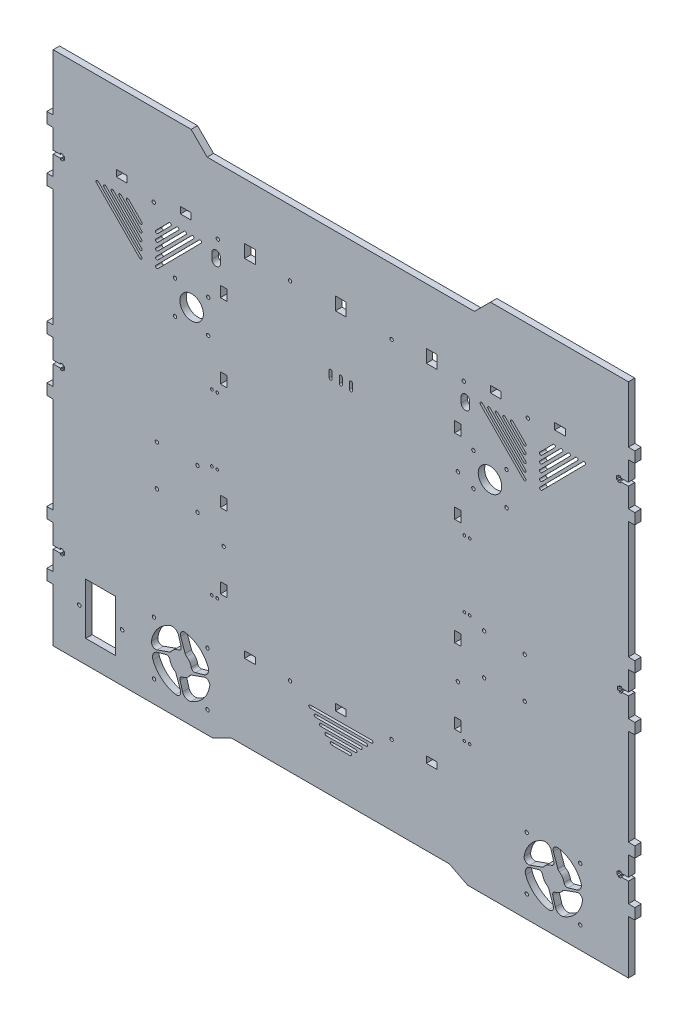
SolidWorks part; units mm, degrees
material "Клен"
ref_plane "Front" through (0, 0, 0) normal (0, 0, 1) x (1, 0, 0)
ref_plane "Top" through (0, 0, 0) normal (0, 1, 0) x (1, 0, 0)
ref_plane "Right" through (0, 0, 0) normal (1, 0, 0) x (0, 0, -1)
sketch "Эскиз1" plane through (0, 0, 0) normal (0, 0, 1) x (1, 0, 0)
  line L3 (1048.7554, 41.5559) -> (1198.2753, 41.5559)
  line L12 (1586.7554, 42.2299) -> (1586.7554, 41.5559)
  line L13 (1397.7554, 445.0072) -> (1407.7554, 445.0072)
  line L14 (1407.7554, 445.0072) -> (1407.7554, 457.1072)
  line L15 (1407.7554, 457.1072) -> (1397.7554, 457.1072)
  line L16 (1397.7554, 457.1072) -> (1397.7554, 445.0072)
  line L17 (1048.7554, 42.2256) -> (1048.7554, 41.5559)
  line L18 (1197.1554, 434.4743) -> (1197.1554, 429.1914)
  line L19 (1503.9666, 426.2291) -> (1516.2724, 438.6716)
  line L20 (1546.3337, 437.0699) -> (1505.9003, 396.1873)
  line L21 (1227.7554, 445.0072) -> (1237.7554, 445.0072)
  line L22 (1237.7554, 445.0072) -> (1237.7554, 457.1072)
  line L23 (1237.7554, 457.1072) -> (1227.7554, 457.1072)
  line L24 (1227.7554, 457.1072) -> (1227.7554, 445.0072)
  line L25 (1312.7554, 445.0072) -> (1322.7554, 445.0072)
  line L26 (1322.7554, 445.0072) -> (1322.7554, 457.1072)
  line L27 (1322.7554, 457.1072) -> (1312.7554, 457.1072)
  line L28 (1312.7554, 457.1072) -> (1312.7554, 445.0072)
  line L38 (1525.1209, 436.9527) -> (1505.7831, 417.4001)
  line L41 (1504.0838, 405.0162) -> (1537.4853, 438.7888)
  line L43 (1504.1228, 397.9452) -> (1544.5562, 438.8279)
  line L44 (1504.0056, 419.1581) -> (1523.3433, 438.7107)
  line L48 (1167.7554, 451.0072) -> (1177.7554, 451.0072)
  line L49 (1177.7554, 451.0072) -> (1177.7554, 457.1072)
  line L50 (1177.7554, 457.1072) -> (1167.7554, 457.1072)
  line L51 (1167.7554, 457.1072) -> (1167.7554, 451.0072)
  line L52 (1518.0499, 436.9136) -> (1505.7441, 424.4711)
  line L53 (1532.1918, 436.9918) -> (1505.8222, 410.3292)
  line L54 (1539.2628, 437.0308) -> (1505.8613, 403.2582)
  line L55 (1504.0447, 412.0872) -> (1530.4143, 438.7498)
  line L56 (1457.7554, 451.0072) -> (1467.7554, 451.0072)
  line L57 (1467.7554, 451.0072) -> (1467.7554, 457.1072)
  line L58 (1467.7554, 457.1072) -> (1457.7554, 457.1072)
  line L59 (1457.7554, 457.1072) -> (1457.7554, 451.0072)
  line L78 (1131.3881, 397.9452) -> (1090.9547, 438.8279)
  line L80 (1089.1772, 437.0699) -> (1129.6105, 396.1873)
  line L82 (1096.2481, 437.0308) -> (1129.6496, 403.2582)
  line L83 (1131.4271, 405.0162) -> (1098.0256, 438.7888)
  line L84 (1131.4662, 412.0872) -> (1105.0966, 438.7498)
  line L85 (1103.3191, 436.9918) -> (1129.6887, 410.3292)
  line L86 (1131.5052, 419.1581) -> (1112.1675, 438.7107)
  line L87 (1110.39, 436.9527) -> (1129.7277, 417.4001)
  line L88 (1131.5443, 426.2291) -> (1119.2385, 438.6716)
  line L89 (1117.461, 436.9136) -> (1129.7668, 424.4711)
  line L90 (1144.921, 397.9452) -> (1185.3543, 438.8279)
  line L91 (1187.1318, 437.0699) -> (1146.6985, 396.1873)
  line L92 (1397.7554, 121.0049) -> (1407.7554, 121.0049)
  line L93 (1407.7554, 121.0049) -> (1407.7554, 127.1049)
  line L94 (1407.7554, 127.1049) -> (1397.7554, 127.1049)
  line L95 (1397.7554, 127.1049) -> (1397.7554, 121.0049)
  line L96 (1312.7554, 121.0049) -> (1322.7554, 121.0049)
  line L97 (1322.7554, 121.0049) -> (1322.7554, 127.1049)
  line L98 (1322.7554, 127.1049) -> (1312.7554, 127.1049)
  line L99 (1312.7554, 127.1049) -> (1312.7554, 121.0049)
  line L100 (1227.7554, 121.0049) -> (1237.7554, 121.0049)
  line L101 (1237.7554, 121.0049) -> (1237.7554, 127.1049)
  line L102 (1237.7554, 127.1049) -> (1227.7554, 127.1049)
  line L143 (1227.7554, 127.1049) -> (1227.7554, 121.0049)
  line L148 (1079.1628, 110.8776) -> (1079.1628, 62.8776)
  line L154 (1455.45, 437.0308) -> (1488.8515, 403.2582)
  line L159 (1107.1628, 110.8776) -> (1079.1628, 110.8776)
  line L160 (1079.1628, 62.8776) -> (1107.1628, 62.8776)
  line L161 (1107.1628, 62.8776) -> (1107.1628, 110.8776)
  line L162 (1144.8819, 405.0162) -> (1178.2834, 438.7888)
  line L163 (1180.0609, 437.0308) -> (1146.6594, 403.2582)
  line L164 (1172.9899, 436.9918) -> (1146.6203, 410.3292)
  line L165 (1144.8428, 412.0872) -> (1171.2124, 438.7498)
  line L166 (1144.8038, 419.1581) -> (1164.1415, 438.7107)
  line L167 (1165.919, 436.9527) -> (1146.5813, 417.4001)
  line L168 (1158.848, 436.9136) -> (1146.5422, 424.4711)
  line L169 (1144.7647, 426.2291) -> (1157.0705, 438.6716)
  line L170 (1205.1554, 429.1914) -> (1205.1554, 434.4743)
  line L171 (1430.3554, 429.1914) -> (1430.3554, 434.4743)
  line L172 (1326.6292, 91.6177) -> (1309.1294, 91.521)
  line L173 (1309.1156, 94.021) -> (1326.6154, 94.1176)
  line L174 (1331.6015, 96.6452) -> (1304.1019, 96.4933)
  line L175 (1304.0881, 98.9933) -> (1331.5877, 99.1452)
  line L176 (1336.5738, 101.6728) -> (1299.0744, 101.4656)
  line L177 (1299.0605, 103.9656) -> (1336.56, 104.1727)
  line L178 (1289.0054, 113.9102) -> (1346.5046, 114.2278)
  line L179 (1346.5184, 111.7279) -> (1289.0193, 111.4102)
  line L180 (1341.5461, 106.7003) -> (1294.0468, 106.4379)
  line L181 (1294.033, 108.9379) -> (1341.5323, 109.2003)
  line L182 (1490.629, 405.0162) -> (1457.2275, 438.7888)
  line L183 (1448.379, 437.0699) -> (1488.8124, 396.1873)
  line L184 (1469.5919, 436.9527) -> (1488.9296, 417.4001)
  line L185 (1476.6629, 436.9136) -> (1488.9687, 424.4711)
  line L186 (1490.5899, 397.9452) -> (1450.1565, 438.8279)
  line L187 (1490.7071, 419.1581) -> (1471.3694, 438.7107)
  line L188 (1462.521, 436.9918) -> (1488.8906, 410.3292)
  line L189 (1490.7462, 426.2291) -> (1478.4404, 438.6716)
  line L198 (1530.3174, 86.3769) -> (1538.4752, 88.7337)
  line L199 (1494.5571, 86.9094) -> (1506.2002, 91.0661)
  line L200 (1517.0418, 100.6255) -> (1514.685, 108.7833)
  line L201 (1502.7664, 87.3542) -> (1494.6086, 84.9974)
  line L202 (1538.538, 86.8062) -> (1526.8948, 82.6495)
  line L203 (1516.0532, 73.09) -> (1518.4101, 64.9322)
  line L204 (1516.4826, 64.8695) -> (1512.3258, 76.5127)
  line L205 (1516.6012, 108.8616) -> (1520.758, 97.2184)
  line L210 (1215.2753, 50.2559) -> (1198.2753, 41.5559)
  line L268 (1215.2753, 50.2559) -> (1419.2753, 50.2559)
  line L269 (1419.2753, 50.2559) -> (1436.2753, 41.5559)
  line L270 (1436.2753, 41.5559) -> (1586.7554, 41.5559)
  line L271 (1490.6681, 412.0872) -> (1464.2985, 438.7498)
  line L302 (1527.7554, 457.1072) -> (1517.7554, 457.1072)
  line L303 (1517.7554, 451.0072) -> (1527.7554, 451.0072)
  line L304 (1517.7554, 457.1072) -> (1517.7554, 451.0072)
  line L305 (1527.7554, 451.0072) -> (1527.7554, 457.1072)
  line L306 (1117.7554, 451.0072) -> (1117.7554, 457.1072)
  line L307 (1107.7554, 457.1072) -> (1107.7554, 451.0072)
  line L308 (1117.7554, 457.1072) -> (1107.7554, 457.1072)
  line L309 (1107.7554, 451.0072) -> (1117.7554, 451.0072)
  line L310 (1167.825, 64.8695) -> (1163.6683, 76.5127)
  line L331 (1438.3554, 434.4743) -> (1438.3554, 429.1914)
  line L332 (1592.7554, 85.0176) -> (1592.7554, 537.1765) construction
  line L333 (989.7428, 524.5559) -> (1177.7554, 524.5559) construction
  line L335 (1048.7554, 524.5559) -> (1177.7554, 524.5559)
  line L337 (1048.7554, 524.5559) -> (1048.7554, 471.6559)
  line L338 (1586.7554, 524.5559) -> (1586.7554, 471.6484)
  line L339 (1442.7554, 509.5559) -> (1457.7554, 524.5559)
  line L342 (1192.7554, 509.5559) -> (1442.7554, 509.5559)
  line L346 (1192.7554, 509.5559) -> (1177.7554, 524.5559)
  line L348 (1592.7554, 461.5645) -> (1586.7554, 461.472)
  line L349 (1457.7554, 524.5559) -> (1617.7234, 524.5559) construction
  line L350 (1457.7554, 524.5559) -> (1586.7554, 524.5559)
  line L358 (1059.2554, 440.0059) -> (1059.2554, 443.1059)
  line L359 (1057.7554, 438.8059) -> (1057.7554, 440.0059)
  line L361 (1057.7554, 270.0059) -> (1059.2554, 270.0059)
  line L362 (1055.5554, 270.0059) -> (1055.5554, 268.8059)
  line L363 (1430.3554, 401.9072) -> (1430.3554, 411.9072)
  line L364 (1430.3554, 411.9072) -> (1424.2554, 411.9072)
  line L365 (1424.2554, 411.9072) -> (1424.2554, 401.9072)
  line L366 (1424.2554, 401.9072) -> (1430.3554, 401.9072)
  line L367 (1430.3554, 331.9072) -> (1430.3554, 341.9072)
  line L368 (1430.3554, 341.9072) -> (1424.2554, 341.9072)
  line L369 (1424.2554, 341.9072) -> (1424.2554, 331.9072)
  line L370 (1424.2554, 331.9072) -> (1430.3554, 331.9072)
  line L371 (1430.3554, 231.9072) -> (1430.3554, 241.9072)
  line L372 (1430.3554, 241.9072) -> (1424.2554, 241.9072)
  line L373 (1424.2554, 241.9072) -> (1424.2554, 231.9072)
  line L374 (1424.2554, 231.9072) -> (1430.3554, 231.9072)
  line L375 (1424.2554, 171.9072) -> (1424.2554, 161.9072)
  line L376 (1424.2554, 161.9072) -> (1430.3554, 161.9072)
  line L377 (1430.3554, 161.9072) -> (1430.3554, 171.9072)
  line L378 (1430.3554, 171.9072) -> (1424.2554, 171.9072)
  line L379 (1205.1554, 161.9072) -> (1211.2554, 161.9072)
  line L380 (1211.2554, 161.9072) -> (1211.2554, 171.9072)
  line L381 (1205.1554, 171.9072) -> (1205.1554, 161.9072)
  line L382 (1211.2554, 171.9072) -> (1205.1554, 171.9072)
  line L383 (1211.2554, 231.9072) -> (1211.2554, 241.9072)
  line L384 (1211.2554, 241.9072) -> (1205.1554, 241.9072)
  line L385 (1205.1554, 241.9072) -> (1205.1554, 231.9072)
  line L386 (1205.1554, 231.9072) -> (1211.2554, 231.9072)
  line L387 (1205.1554, 331.9072) -> (1211.2554, 331.9072)
  line L388 (1211.2554, 331.9072) -> (1211.2554, 341.9072)
  line L389 (1205.1554, 341.9072) -> (1205.1554, 331.9072)
  line L390 (1211.2554, 341.9072) -> (1205.1554, 341.9072)
  line L391 (1205.1554, 401.9072) -> (1211.2554, 401.9072)
  line L392 (1211.2554, 401.9072) -> (1211.2554, 411.9072)
  line L393 (1211.2554, 411.9072) -> (1205.1554, 411.9072)
  line L394 (1205.1554, 411.9072) -> (1205.1554, 401.9072)
  line L395 (1145.8995, 86.9094) -> (1157.5427, 91.0661)
  line L396 (1189.8804, 86.8062) -> (1178.2373, 82.6495)
  line L397 (1167.3957, 73.09) -> (1169.7525, 64.9322)
  line L398 (1154.1089, 87.3542) -> (1145.951, 84.9974)
  line L399 (1181.6599, 86.3769) -> (1189.8177, 88.7337)
  line L400 (1167.9437, 108.8616) -> (1172.1004, 97.2184)
  line L414 (1057.7554, 118.8059) -> (1057.7554, 120.0059)
  line L415 (1168.3843, 100.6255) -> (1166.0274, 108.7833)
  line L416 (1317.7554, 12.4246) -> (1317.7554, 537.1765) construction
  line L417 (1586.7554, 537.1765) -> (1586.7554, 12.4246) construction
  line L418 (1048.7554, 537.1765) -> (1048.7554, -11.6164) construction
  line L419 (1042.7554, 91.5559) -> (1042.7554, 101.5559)
  line L422 (1048.7554, 123.1059) -> (1048.7554, 141.4559)
  line L426 (1059.2554, 123.1059) -> (1057.7554, 123.1059)
  line L427 (1057.7554, 274.3059) -> (1055.5554, 274.3059)
  line L428 (1325.8554, 394.0442) -> (1325.8554, 388.0442)
  line L429 (1328.6554, 388.0442) -> (1328.6554, 394.0442)
  line L430 (1042.7554, 101.5559) -> (1048.7554, 101.6559)
  line L431 (1057.7554, 120.0059) -> (1059.2554, 120.0059)
  line L432 (1316.3554, 394.0442) -> (1316.3554, 388.0442)
  line L433 (1319.1554, 388.0442) -> (1319.1554, 394.0442)
  line L434 (1042.7554, 141.5559) -> (1042.7554, 151.5559)
  line L435 (1042.7554, 301.5559) -> (1048.7554, 301.6559)
  line L436 (1306.8554, 394.0442) -> (1306.8554, 388.0442)
  line L437 (1309.6554, 388.0442) -> (1309.6554, 394.0442)
  line L438 (1055.5554, 120.0059) -> (1055.5554, 118.8059)
  line L439 (1048.7554, 411.4559) -> (1042.7554, 411.5559)
  line L440 (1055.5554, 444.3059) -> (1055.5554, 443.1059)
  line L441 (1057.7554, 124.3059) -> (1055.5554, 124.3059)
  line L442 (1055.5554, 443.1059) -> (1048.7554, 443.1059)
  line L443 (1048.7554, 120.0059) -> (1055.5554, 120.0059)
  line L444 (1042.7554, 241.5559) -> (1042.7554, 251.5559)
  line L445 (1055.5554, 268.8059) -> (1057.7554, 268.8059)
  line L446 (1055.5554, 274.3059) -> (1055.5554, 273.1059)
  line L447 (1048.7554, 461.4559) -> (1042.7554, 461.5559)
  line L448 (1048.7554, 101.6559) -> (1048.7554, 120.0059)
  line L449 (1057.7554, 440.0059) -> (1059.2554, 440.0059)
  line L450 (1048.7554, 251.6559) -> (1048.7554, 270.0059)
  line L451 (1042.7554, 291.5559) -> (1042.7554, 301.5559)
  line L452 (1042.7554, 471.5559) -> (1048.7554, 471.6559)
  line L453 (1059.2554, 443.1059) -> (1057.7554, 443.1059)
  line L454 (1048.7554, 42.2256) -> (1048.7554, 91.4559)
  line L455 (1048.7554, 273.1059) -> (1048.7554, 291.4559)
  line L456 (1055.5554, 440.0059) -> (1055.5554, 438.8059)
  line L457 (1055.5554, 438.8059) -> (1057.7554, 438.8059)
  line L458 (1042.7554, 421.5559) -> (1048.7554, 421.6559)
  line L459 (1048.7554, 443.1059) -> (1048.7554, 461.4559)
  line L460 (1048.7554, 141.4559) -> (1042.7554, 141.5559)
  line L461 (1048.7554, 301.6559) -> (1048.7554, 411.4559)
  line L462 (1048.7554, 91.4559) -> (1042.7554, 91.5559)
  line L463 (1048.7554, 270.0059) -> (1055.5554, 270.0059)
  line L464 (1048.7554, 291.4559) -> (1042.7554, 291.5559)
  line L465 (1059.2554, 120.0059) -> (1059.2554, 123.1059)
  line L466 (1057.7554, 273.1059) -> (1057.7554, 274.3059)
  line L467 (1042.7554, 251.5559) -> (1048.7554, 251.6559)
  line L468 (1059.2554, 273.1059) -> (1057.7554, 273.1059)
  line L469 (1048.7554, 421.6559) -> (1048.7554, 440.0059)
  line L470 (1042.7554, 461.5559) -> (1042.7554, 471.5559)
  line L471 (1057.7554, 268.8059) -> (1057.7554, 270.0059)
  line L472 (1057.7554, 443.1059) -> (1057.7554, 444.3059)
  line L473 (1042.7554, 151.5559) -> (1048.7554, 151.6559)
  line L474 (1059.2554, 270.0059) -> (1059.2554, 273.1059)
  line L475 (1055.5554, 273.1059) -> (1048.7554, 273.1059)
  line L476 (1048.7554, 151.6559) -> (1048.7554, 241.4559)
  line L477 (1057.7554, 444.3059) -> (1055.5554, 444.3059)
  line L478 (1055.5554, 124.3059) -> (1055.5554, 123.1059)
  line L479 (1048.7554, 241.4559) -> (1042.7554, 241.5559)
  line L480 (1055.5554, 123.1059) -> (1048.7554, 123.1059)
  line L481 (1057.7554, 123.1059) -> (1057.7554, 124.3059)
  line L482 (1055.5554, 118.8059) -> (1057.7554, 118.8059)
  line L483 (1042.7554, 411.5559) -> (1042.7554, 421.5559)
  line L484 (1048.7554, 440.0059) -> (1055.5554, 440.0059)
  line L488 (1586.7554, 301.6559) -> (1592.7554, 301.5559)
  line L489 (1592.7554, 251.5803) -> (1592.7554, 241.5722)
  line L490 (1579.2472, 444.3102) -> (1577.0472, 444.3102)
  line L491 (1592.7554, 471.5559) -> (1592.7554, 461.5645)
  line L492 (1579.9554, 120.0141) -> (1586.7554, 120.0141)
  line L493 (1592.7554, 101.5641) -> (1592.7554, 91.5559)
  line L494 (1579.9554, 123.1141) -> (1579.9554, 124.3141)
  line L496 (1577.7554, 120.0141) -> (1577.7554, 118.8141)
  line L497 (1578.2356, 268.8303) -> (1580.4356, 268.8303)
  line L498 (1575.5472, 440.0102) -> (1577.0472, 440.0102)
  line L499 (1580.4356, 274.3303) -> (1578.2356, 274.3303)
  line L500 (1577.7554, 123.1141) -> (1576.2554, 123.1141)
  line L501 (1576.7356, 273.1303) -> (1576.7356, 270.0303)
  line L502 (1586.0472, 443.1102) -> (1586.7554, 443.1102)
  line L503 (1578.2356, 274.3303) -> (1578.2356, 273.1303)
  line L504 (1577.0472, 438.8102) -> (1579.2472, 438.8102)
  line L505 (1576.2554, 120.0141) -> (1577.7554, 120.0141)
  line L506 (1586.0472, 443.1102) -> (1579.2472, 443.1102)
  line L507 (1586.7554, 141.4641) -> (1586.7554, 123.1141)
  line L508 (1592.7554, 141.5641) -> (1586.7554, 141.4641)
  line L509 (1586.7554, 251.6803) -> (1592.7554, 251.5803)
  line L510 (1578.2356, 270.0303) -> (1578.2356, 268.8303)
  line L511 (1580.4356, 270.0303) -> (1586.7554, 270.0303)
  line L512 (1579.9554, 124.3141) -> (1577.7554, 124.3141)
  line L513 (1577.7554, 124.3141) -> (1577.7554, 123.1141)
  line L514 (1592.7554, 141.5641) -> (1592.7554, 151.5722)
  line L515 (1579.2472, 440.0102) -> (1586.0472, 440.0102)
  line L516 (1592.7554, 411.5559) -> (1586.7554, 411.4559)
  line L517 (1580.4356, 268.8303) -> (1580.4356, 270.0303)
  line L518 (1586.7554, 91.4559) -> (1586.7554, 42.2299)
  line L519 (1592.7554, 241.5722) -> (1586.7554, 241.4722)
  line L520 (1579.2472, 438.8102) -> (1579.2472, 440.0102)
  line L521 (1580.4356, 273.1303) -> (1580.4356, 274.3303)
  line L522 (1586.7554, 270.0303) -> (1586.7554, 251.6803)
  line L523 (1577.0472, 443.1102) -> (1575.5472, 443.1102)
  line L524 (1586.7554, 151.6722) -> (1592.7554, 151.5722)
  line L525 (1577.7554, 118.8141) -> (1579.9554, 118.8141)
  line L526 (1592.7554, 421.5559) -> (1592.7554, 411.5559)
  line L527 (1586.7554, 421.6484) -> (1592.7554, 421.5559)
  line L528 (1579.9554, 118.8141) -> (1579.9554, 120.0141)
  line L529 (1586.7554, 273.1303) -> (1580.4356, 273.1303)
  line L530 (1586.7554, 123.1141) -> (1579.9554, 123.1141)
  line L531 (1586.0472, 440.0102) -> (1586.7554, 440.0102)
  line L532 (1576.7356, 270.0303) -> (1578.2356, 270.0303)
  line L533 (1586.7554, 461.472) -> (1586.7554, 443.1102)
  line L534 (1575.5472, 443.1102) -> (1575.5472, 440.0102)
  line L535 (1592.7554, 291.5478) -> (1586.7554, 291.4478)
  line L536 (1586.7554, 120.0141) -> (1586.7554, 101.6641)
  line L537 (1576.2554, 123.1141) -> (1576.2554, 120.0141)
  line L538 (1586.7554, 101.6641) -> (1592.7554, 101.5641)
  line L539 (1592.7554, 91.5559) -> (1586.7554, 91.4559)
  line L540 (1586.7554, 411.4559) -> (1586.7554, 301.6559)
  line L541 (1592.7554, 301.5559) -> (1592.7554, 291.5478)
  line L542 (1577.0472, 444.3102) -> (1577.0472, 443.1102)
  line L543 (1579.2472, 443.1102) -> (1579.2472, 444.3102)
  line L544 (1586.7554, 241.4722) -> (1586.7554, 151.6722)
  line L545 (1586.7554, 440.0102) -> (1586.7554, 421.6484)
  line L546 (1586.7554, 291.4478) -> (1586.7554, 273.1303)
  line L547 (1578.2356, 273.1303) -> (1576.7356, 273.1303)
  line L548 (1586.7554, 471.6484) -> (1592.7554, 471.5559)
  line L549 (1577.0472, 440.0102) -> (1577.0472, 438.8102)
  circle A0 centre (1193.7068, 365.5072) radius 1.6
  circle A1 centre (1162.7068, 365.5072) radius 1.6
  circle A2 centre (1178.2068, 380.5559) radius 11
  circle A3 centre (1193.7068, 396.5072) radius 1.6
  circle A4 centre (1202.7554, 448.0572) radius 1.6
  circle A5 centre (1432.7554, 448.0572) radius 1.6
  circle A6 centre (1365.2554, 448.0572) radius 1.6
  circle A7 centre (1270.2554, 448.0572) radius 1.6
  circle A12 centre (1162.7068, 396.5072) radius 1.6
  circle A13 centre (1145.7129, 217.2739) radius 1.6
  circle A14 centre (1365.2554, 124.0549) radius 1.6
  circle A15 centre (1270.2554, 124.0549) radius 1.6
  circle A20 centre (1492.7554, 448.0572) radius 1.6
  circle A21 centre (1142.7554, 448.0572) radius 1.6
  circle A24 centre (1073.1628, 86.8776) radius 1.65
  circle A25 centre (1113.1628, 86.8776) radius 1.65
  circle A26 centre (1145.7129, 255.2739) radius 1.6
  circle A27 centre (1183.7129, 217.2739) radius 1.6
  circle A28 centre (1183.7129, 255.2739) radius 1.6
  arc A29 (1504.0056, 419.1581) -> (1505.7831, 417.4001) centre (1504.8944, 418.2791) ccw
  arc A30 (1503.9666, 426.2291) -> (1505.7441, 424.4711) centre (1504.8553, 425.3501) ccw
  arc A31 (1504.1228, 397.9452) -> (1505.9003, 396.1873) centre (1505.0116, 397.0662) ccw
  arc A32 (1518.0499, 436.9136) -> (1516.2724, 438.6716) centre (1517.1611, 437.7926) ccw
  arc A33 (1504.0447, 412.0872) -> (1505.8222, 410.3292) centre (1504.9335, 411.2082) ccw
  arc A34 (1546.3337, 437.0699) -> (1544.5562, 438.8279) centre (1545.445, 437.9489) ccw
  arc A35 (1539.2628, 437.0308) -> (1537.4853, 438.7888) centre (1538.374, 437.9098) ccw
  arc A36 (1326.6292, 91.6177) -> (1326.6154, 94.1176) centre (1326.6223, 92.8677) ccw
  arc A37 (1309.1156, 94.021) -> (1309.1294, 91.521) centre (1309.1225, 92.771) ccw
  arc A38 (1304.0881, 98.9933) -> (1304.1019, 96.4933) centre (1304.095, 97.7433) ccw
  arc A39 (1331.6015, 96.6452) -> (1331.5877, 99.1452) centre (1331.5946, 97.8952) ccw
  arc A40 (1336.5738, 101.6728) -> (1336.56, 104.1727) centre (1336.5669, 102.9228) ccw
  arc A41 (1299.0605, 103.9656) -> (1299.0744, 101.4656) centre (1299.0674, 102.7156) ccw
  arc A42 (1294.033, 108.9379) -> (1294.0468, 106.4379) centre (1294.0399, 107.6879) ccw
  arc A43 (1341.5461, 106.7003) -> (1341.5323, 109.2003) centre (1341.5392, 107.9503) ccw
  arc A44 (1346.5184, 111.7279) -> (1346.5046, 114.2278) centre (1346.5115, 112.9779) ccw
  arc A45 (1289.0054, 113.9102) -> (1289.0193, 111.4102) centre (1289.0124, 112.6602) ccw
  arc A46 (1157.5427, 91.0661) -> (1159.5017, 92.5785) centre (1156.1978, 94.8332) ccw
  arc A47 (1450.1565, 438.8279) -> (1448.379, 437.0699) centre (1449.2678, 437.9489) ccw
  arc A48 (1471.3694, 438.7107) -> (1469.5919, 436.9527) centre (1470.4807, 437.8317) ccw
  arc A49 (1457.2275, 438.7888) -> (1455.45, 437.0308) centre (1456.3388, 437.9098) ccw
  arc A50 (1488.9687, 424.4711) -> (1490.7462, 426.2291) centre (1489.8574, 425.3501) ccw
  arc A51 (1488.8515, 403.2582) -> (1490.629, 405.0162) centre (1489.7403, 404.1372) ccw
  arc A52 (1488.8124, 396.1873) -> (1490.5899, 397.9452) centre (1489.7012, 397.0662) ccw
  arc A53 (1488.8906, 410.3292) -> (1490.6681, 412.0872) centre (1489.7793, 411.2082) ccw
  arc A54 (1488.9296, 417.4001) -> (1490.7071, 419.1581) centre (1489.8184, 418.2791) ccw
  arc A55 (1478.4404, 438.6716) -> (1476.6629, 436.9136) centre (1477.5516, 437.7926) ccw
  arc A56 (1464.2985, 438.7498) -> (1462.521, 436.9918) centre (1463.4097, 437.8708) ccw
  arc A67 (1166.0274, 108.7833) -> (1158.15, 112.7336) centre (1160.2632, 107.118) ccw
  arc A68 (1189.8177, 88.7337) -> (1193.7679, 96.6112) centre (1188.1523, 94.498) ccw
  circle A69 centre (1143.0318, 112.013) radius 1.6
  circle A70 centre (1143.0318, 62.013) radius 1.6
  arc A71 (1166.0477, 96.8429) -> (1168.3843, 100.6255) centre (1165.5021, 99.7929) ccw
  arc A72 (1145.951, 84.9974) -> (1142.0008, 77.1199) centre (1147.6164, 79.2331) ccw
  arc A100 (1178.2373, 82.6495) -> (1176.2782, 81.1371) centre (1179.5822, 78.8823) ccw
  arc A102 (1538.4752, 88.7337) -> (1542.4254, 96.6112) centre (1536.8099, 94.498) ccw
  arc A103 (1526.2875, 60.982) -> (1543.8306, 82.3942) centre (1516.5531, 86.85) ccw
  arc A104 (1512.3258, 76.5127) -> (1510.8135, 78.4717) centre (1508.5587, 75.1677) ccw
  arc A105 (1518.3898, 76.8727) -> (1516.0532, 73.09) centre (1518.9354, 73.9227) ccw
  arc A106 (1489.2645, 91.3213) -> (1494.5571, 86.9094) centre (1493.2122, 90.6765) ccw
  arc A107 (1512.0706, 59.5769) -> (1516.4826, 64.8695) centre (1512.7155, 63.5246) ccw
  arc A108 (1506.2002, 91.0661) -> (1508.1593, 92.5785) centre (1504.8553, 94.8332) ccw
  arc A109 (1521.0132, 114.1542) -> (1516.6012, 108.8616) centre (1520.3684, 110.2065) ccw
  arc A110 (1518.3898, 76.8727) -> (1524.9358, 81.1371) centre (1516.5419, 86.8655) ccw
  circle A111 centre (1541.6893, 112.013) radius 1.6
  arc A112 (1494.6086, 84.9974) -> (1490.6584, 77.1199) centre (1496.2739, 79.2331) ccw
  arc A113 (1506.5491, 85.0176) -> (1510.8135, 78.4717) centre (1516.5419, 86.8655) ccw
  arc A114 (1526.8948, 82.6495) -> (1524.9358, 81.1371) centre (1528.2397, 78.8823) ccw
  circle A115 centre (1541.6893, 62.013) radius 1.6
  arc A116 (1490.6584, 77.1199) -> (1512.0706, 59.5769) centre (1516.5264, 86.8543) ccw
  arc A117 (1514.685, 108.7833) -> (1506.8075, 112.7336) centre (1508.9207, 107.118) ccw
  circle A118 centre (1491.6893, 112.013) radius 1.6
  arc A119 (1520.758, 97.2184) -> (1522.2703, 95.2594) centre (1524.5251, 98.5634) ccw
  arc A120 (1542.4254, 96.6112) -> (1521.0132, 114.1542) centre (1516.5574, 86.8768) ccw
  arc A121 (1526.5348, 88.7135) -> (1522.2703, 95.2594) centre (1516.5419, 86.8655) ccw
  arc A122 (1506.8075, 112.7336) -> (1489.2645, 91.3213) centre (1516.5419, 86.8655) ccw
  arc A123 (1506.5491, 85.0176) -> (1502.7664, 87.3542) centre (1503.5991, 84.4721) ccw
  arc A124 (1514.7052, 96.8429) -> (1508.1593, 92.5785) centre (1516.5531, 86.85) ccw
  arc A125 (1543.8306, 82.3942) -> (1538.538, 86.8062) centre (1539.8829, 83.0391) ccw
  circle A126 centre (1491.6893, 62.013) radius 1.6
  arc A127 (1518.4101, 64.9322) -> (1526.2875, 60.982) centre (1524.1743, 66.5976) ccw
  arc A128 (1526.5348, 88.7135) -> (1530.3174, 86.3769) centre (1529.4848, 89.259) ccw
  arc A129 (1514.7052, 96.8429) -> (1517.0418, 100.6255) centre (1514.1597, 99.7929) ccw
  arc A130 (1157.8915, 85.0176) -> (1154.1089, 87.3542) centre (1154.9415, 84.4721) ccw
  arc A131 (1172.3557, 114.1542) -> (1167.9437, 108.8616) centre (1171.7108, 110.2065) ccw
  arc A132 (1172.1004, 97.2184) -> (1173.6128, 95.2594) centre (1175.8676, 98.5634) ccw
  arc A133 (1177.63, 60.982) -> (1195.173, 82.3942) centre (1167.8956, 86.85) ccw
  arc A134 (1193.7679, 96.6112) -> (1172.3557, 114.1542) centre (1167.8999, 86.8768) ccw
  circle A135 centre (1193.0318, 62.013) radius 1.6
  arc A136 (1166.0477, 96.8429) -> (1159.5017, 92.5785) centre (1167.8956, 86.85) ccw
  arc A137 (1169.7525, 64.9322) -> (1177.63, 60.982) centre (1175.5168, 66.5976) ccw
  arc A138 (1169.7323, 76.8727) -> (1176.2782, 81.1371) centre (1167.8844, 86.8655) ccw
  arc A139 (1177.8772, 88.7135) -> (1173.6128, 95.2594) centre (1167.8844, 86.8655) ccw
  arc A160 (1169.7323, 76.8727) -> (1167.3957, 73.09) centre (1170.2778, 73.9227) ccw
  arc A161 (1157.8915, 85.0176) -> (1162.1559, 78.4717) centre (1167.8844, 86.8655) ccw
  arc A162 (1163.4131, 59.5769) -> (1167.825, 64.8695) centre (1164.0579, 63.5246) ccw
  arc A163 (1142.0008, 77.1199) -> (1163.4131, 59.5769) centre (1167.8688, 86.8543) ccw
  arc A164 (1163.6683, 76.5127) -> (1162.1559, 78.4717) centre (1159.9012, 75.1677) ccw
  arc A165 (1195.173, 82.3942) -> (1189.8804, 86.8062) centre (1191.2253, 83.0391) ccw
  arc A166 (1177.8772, 88.7135) -> (1181.6599, 86.3769) centre (1180.8272, 89.259) ccw
  circle A167 centre (1193.0318, 112.013) radius 1.6
  arc A168 (1158.15, 112.7336) -> (1140.6069, 91.3213) centre (1167.8844, 86.8655) ccw
  arc A169 (1140.6069, 91.3213) -> (1145.8995, 86.9094) centre (1144.5546, 90.6765) ccw
  arc A190 (1532.1918, 436.9918) -> (1530.4143, 438.7498) centre (1531.3031, 437.8708) ccw
  arc A191 (1525.1209, 436.9527) -> (1523.3433, 438.7107) centre (1524.2321, 437.8317) ccw
  arc A192 (1504.0838, 405.0162) -> (1505.8613, 403.2582) centre (1504.9725, 404.1372) ccw
  arc A193 (1089.1772, 437.0699) -> (1090.9547, 438.8279) centre (1090.0659, 437.9489) cw
  circle A194 centre (1427.3054, 371.9072) radius 1.6
  circle A195 centre (1427.3054, 201.9072) radius 1.6
  circle A196 centre (1208.2054, 201.9072) radius 1.6
  arc A198 (1131.3881, 397.9452) -> (1129.6105, 396.1873) centre (1130.4993, 397.0662) cw
  arc A199 (1131.4271, 405.0162) -> (1129.6496, 403.2582) centre (1130.5384, 404.1372) cw
  arc A200 (1096.2481, 437.0308) -> (1098.0256, 438.7888) centre (1097.1369, 437.9098) cw
  arc A201 (1103.3191, 436.9918) -> (1105.0966, 438.7498) centre (1104.2078, 437.8708) cw
  arc A202 (1131.4662, 412.0872) -> (1129.6887, 410.3292) centre (1130.5774, 411.2082) cw
  arc A203 (1110.39, 436.9527) -> (1112.1675, 438.7107) centre (1111.2788, 437.8317) cw
  arc A216 (1131.5052, 419.1581) -> (1129.7277, 417.4001) centre (1130.6165, 418.2791) cw
  arc A217 (1117.461, 436.9136) -> (1119.2385, 438.6716) centre (1118.3497, 437.7926) cw
  arc A218 (1131.5443, 426.2291) -> (1129.7668, 424.4711) centre (1130.6556, 425.3501) cw
  arc A219 (1146.6985, 396.1873) -> (1144.921, 397.9452) centre (1145.8097, 397.0662) cw
  circle A220 centre (1202.1959, 261.1916) radius 1.25
  circle A221 centre (1197.2245, 261.2595) radius 1.25
  circle A228 centre (1202.1586, 156.838) radius 1.25
  circle A229 centre (1197.1872, 156.9059) radius 1.25
  arc A230 (1185.3543, 438.8279) -> (1187.1318, 437.0699) centre (1186.2431, 437.9489) cw
  arc A231 (1178.2834, 438.7888) -> (1180.0609, 437.0308) centre (1179.1721, 437.9098) cw
  circle A232 centre (1438.3088, 156.7702) radius 1.25
  arc A233 (1146.6594, 403.2582) -> (1144.8819, 405.0162) centre (1145.7706, 404.1372) cw
  circle A234 centre (1433.3374, 156.838) radius 1.25
  arc A235 (1171.2124, 438.7498) -> (1172.9899, 436.9918) centre (1172.1012, 437.8708) cw
  arc A237 (1146.6203, 410.3292) -> (1144.8428, 412.0872) centre (1145.7316, 411.2082) cw
  arc A239 (1146.5813, 417.4001) -> (1144.8038, 419.1581) centre (1145.6925, 418.2791) cw
  arc A241 (1164.1415, 438.7107) -> (1165.919, 436.9527) centre (1165.0302, 437.8317) cw
  arc A243 (1157.0705, 438.6716) -> (1158.848, 436.9136) centre (1157.9593, 437.7926) cw
  arc A245 (1146.5422, 424.4711) -> (1144.7647, 426.2291) centre (1145.6534, 425.3501) cw
  circle A247 centre (1472.8041, 365.5072) radius 1.6
  circle A248 centre (1438.3461, 261.1238) radius 1.25
  circle A249 centre (1441.8041, 365.5072) radius 1.6
  circle A250 centre (1433.3748, 261.1916) radius 1.25
  circle A251 centre (1441.8041, 396.5072) radius 1.6
  circle A252 centre (1438.3268, 323.4135) radius 1.25
  circle A253 centre (1457.3041, 380.5559) radius 11
  circle A254 centre (1433.3554, 323.4814) radius 1.25
  circle A255 centre (1472.8041, 396.5072) radius 1.6
  circle A256 centre (1489.798, 217.2739) radius 1.6
  circle A257 centre (1451.798, 217.2739) radius 1.6
  circle A261 centre (1451.798, 255.2739) radius 1.6
  circle A263 centre (1489.798, 255.2739) radius 1.6
  arc A265 (1201.1554, 438.4743) -> (1197.1554, 434.4743) centre (1201.1554, 434.4743) ccw
  arc A267 (1205.1554, 434.4743) -> (1201.1554, 438.4743) centre (1201.1554, 434.4743) ccw
  arc A269 (1197.1554, 429.1914) -> (1201.1554, 425.1914) centre (1201.1554, 429.1914) ccw
  arc A271 (1201.1554, 425.1914) -> (1205.1554, 429.1914) centre (1201.1554, 429.1914) ccw
  arc A273 (1434.3554, 438.4743) -> (1438.3554, 434.4743) centre (1434.3554, 434.4743) cw
  arc A275 (1430.3554, 434.4743) -> (1434.3554, 438.4743) centre (1434.3554, 434.4743) cw
  arc A277 (1434.3554, 425.1914) -> (1430.3554, 429.1914) centre (1434.3554, 429.1914) cw
  arc A279 (1438.3554, 429.1914) -> (1434.3554, 425.1914) centre (1434.3554, 429.1914) cw
  circle A280 centre (1202.1766, 323.4814) radius 1.25
  circle A282 centre (1197.2052, 323.5492) radius 1.25
  arc A312 (1325.8554, 388.0442) -> (1328.6554, 388.0442) centre (1327.2554, 388.0442) ccw
  arc A313 (1328.6554, 394.0442) -> (1325.8554, 394.0442) centre (1327.2554, 394.0442) ccw
  arc A316 (1316.3554, 388.0442) -> (1319.1554, 388.0442) centre (1317.7554, 388.0442) ccw
  arc A317 (1319.1554, 394.0442) -> (1316.3554, 394.0442) centre (1317.7554, 394.0442) ccw
  arc A320 (1306.8554, 388.0442) -> (1309.6554, 388.0442) centre (1308.2554, 388.0442) ccw
  arc A321 (1309.6554, 394.0442) -> (1306.8554, 394.0442) centre (1308.2554, 394.0442) ccw
  point P31 (1317.7554, 524.5559)
  dimension "D3" = 269
  dimension "D4" = 15.5
  dimension "D5" = 31
  dimension "D6" = 31
  dimension "D2" = 269
  dimension "D8" = 31
  dimension "D1" = 149.5198
  dimension "D7" = 250
  dimension "D10" = 6
extrude "Бобышка-Вытянуть1" add sketch "Эскиз1" against normal blind 6
